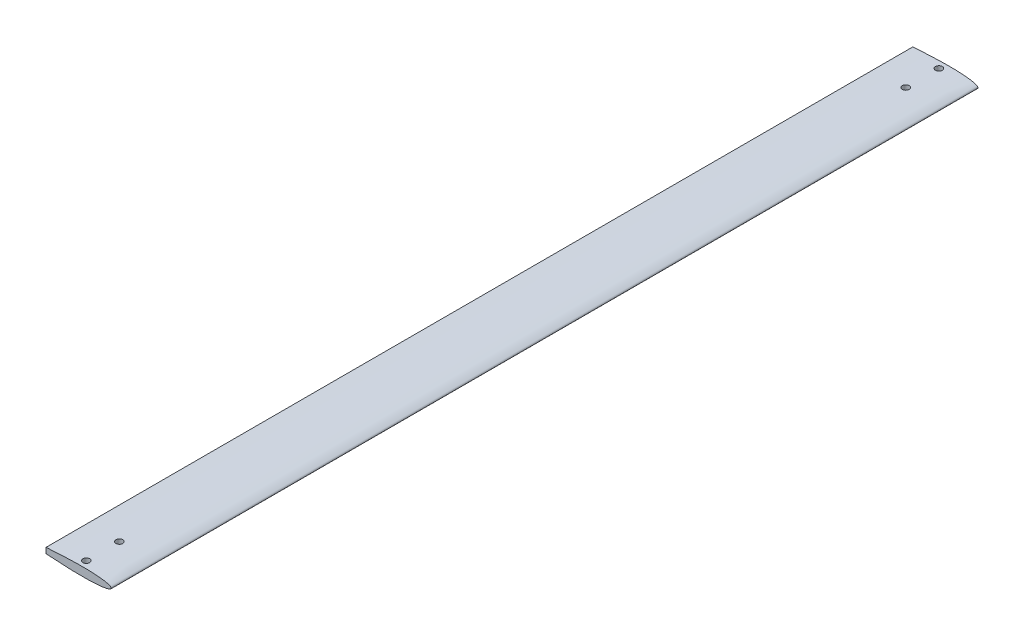
SolidWorks part; units mm, degrees
ref_plane "Front Plane" through (0, 0, 0) normal (0, 0, 1) x (1, 0, 0)
ref_plane "Top Plane" through (0, 0, 0) normal (0, 1, 0) x (1, 0, 0)
ref_plane "Right Plane" through (0, 0, 0) normal (1, 0, 0) x (0, 0, -1)
sketch "Sketch1" plane through (0, 0, 0) normal (0, 0, 1) x (1, 0, 0)
  line L0 (-69.0363, 2.9326) -> (-69.0363, -2.9326)
  spline S0 degree 3 poles (-69.0363, 2.9326) (-68.1737, 2.9942) (-65.6011, 3.1782) (-61.2784, 3.4568) (-56.0498, 3.7659) (-50.7631, 4.0385) (-45.4763, 4.2662) (-40.2474, 4.4388) (-35.1335, 4.5471) (-30.1906, 4.583) (-25.4729, 4.5402) (-21.0319, 4.4149) (-16.9162, 4.2059) (-13.1707, 3.9149) (-9.8363, 3.5464) (-6.9481, 3.1082) (-4.5376, 2.6073) (-2.6226, 2.0608) (-1.2236, 1.4608) (-0.2915, 0.8409) (0.1205, 0) (-0.2915, -0.8409) (-1.2236, -1.4608) (-2.6226, -2.0608) (-4.5376, -2.6073) (-6.9481, -3.1082) (-9.8363, -3.5464) (-13.1707, -3.9149) (-16.9162, -4.2059) (-21.0319, -4.4149) (-25.4729, -4.5402) (-30.1906, -4.583) (-35.1335, -4.5471) (-40.2474, -4.4388) (-45.4763, -4.2662) (-50.7631, -4.0385) (-56.0498, -3.7659) (-61.2784, -3.4568) (-65.6011, -3.1782) (-68.1737, -2.9942) (-69.0363, -2.9326) knots 0 0 0 0 0.018499 0.055171 0.092655 0.130539 0.168407 0.205846 0.242449 0.277819 0.311577 0.343364 0.372846 0.399719 0.423712 0.444594 0.46218 0.476354 0.487106 0.494669 0.5 0.505331 0.512894 0.523646 0.53782 0.555406 0.576288 0.600281 0.627154 0.656636 0.688423 0.722181 0.757551 0.794154 0.831593 0.869461 0.907345 0.944829 0.981501 1 1 1 1
extrude "Boss-Extrude1" add sketch "Sketch1" along normal mid plane 917.4
ref_plane "Plane1" through (0, -10, 0) normal (0, 1, 0) x (1, 0, 0)
sketch "Sketch2" plane through (0, -10, 0) normal (0, 1, 0) x (1, 0, 0)
  circle A0 centre (-33.9, -451.2) radius 3.6
  circle A1 centre (-33.9, -416.2) radius 3.6
  circle A2 centre (-33.9, 416.2) radius 3.6
  circle A3 centre (-33.9, 451.2) radius 3.6
extrude "Cut-Extrude1" cut sketch "Sketch2" along normal blind 20
